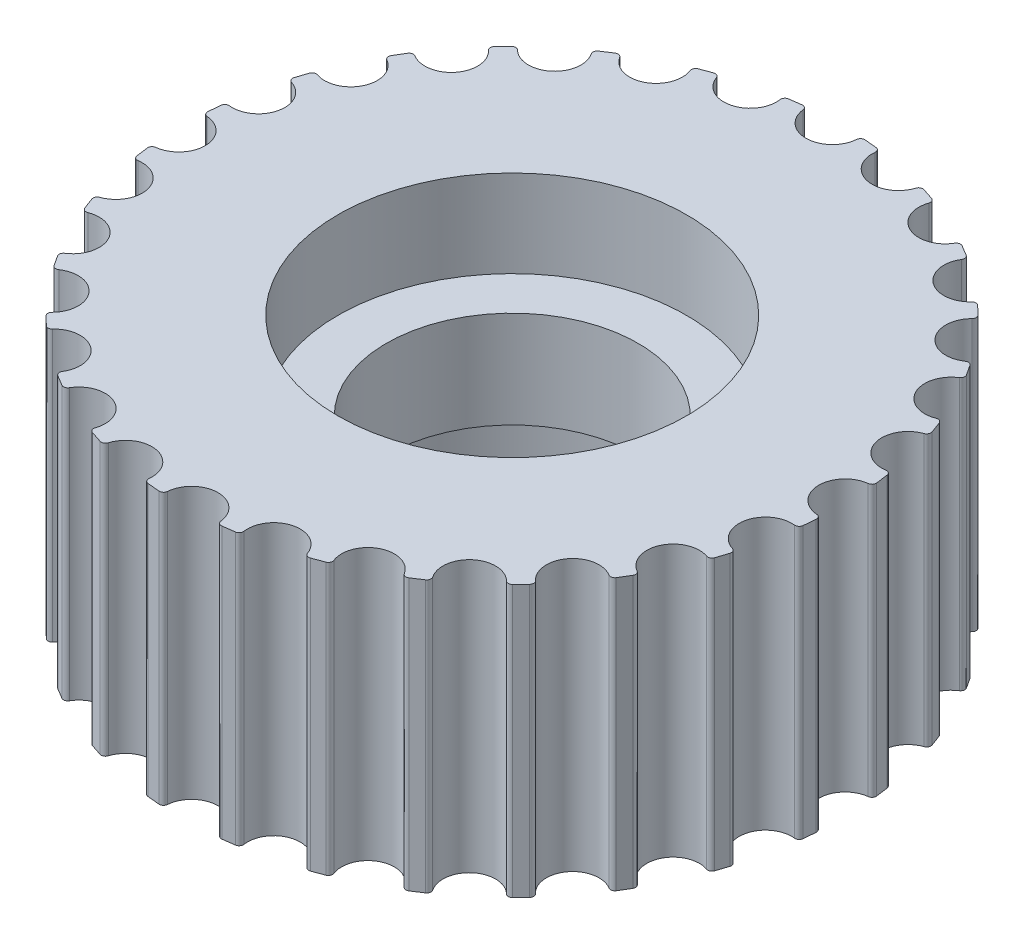
SolidWorks part; units mm, degrees
ref_plane "Front Plane" through (0, 0, 0) normal (0, 0, 1) x (1, 0, 0)
ref_plane "Top Plane" through (0, 0, 0) normal (0, 1, 0) x (1, 0, 0)
ref_plane "Right Plane" through (0, 0, 0) normal (1, 0, 0) x (0, 0, -1)
sketch "Sketch1" plane through (0, 0, 0) normal (0, 1, 0) x (1, 0, 0)
  line L0 (-1.2729, 8.4042) -> (-0.9622, 8.4454)
  line L1 (0.6306, 8.4766) -> (0.9426, 8.4476)
  line L2 (2.5024, 8.1236) -> (2.8002, 8.026)
  line L3 (4.2488, 7.363) -> (4.5174, 7.2015)
  line L4 (5.7821, 6.2329) -> (6.008, 6.0157)
  line L5 (7.0255, 4.7898) -> (7.1974, 4.5278)
  line L6 (7.9167, 3.1063) -> (8.026, 2.8126)
  line L7 (8.4108, 1.2667) -> (8.452, 0.9561)
  line L8 (8.4833, -0.6368) -> (8.4543, -0.9488)
  line L9 (8.1303, -2.5086) -> (8.0326, -2.8064)
  line L10 (7.3697, -4.255) -> (7.2082, -4.5235)
  line L11 (6.2395, -5.7883) -> (6.0223, -6.0142)
  line L12 (4.7965, -7.0317) -> (4.5345, -7.2036)
  line L13 (3.113, -7.9228) -> (2.8193, -8.0321)
  line L14 (1.2734, -8.417) -> (0.9627, -8.4582)
  line L15 (-0.6301, -8.4894) -> (-0.9421, -8.4605)
  line L16 (-2.5019, -8.1365) -> (-2.7997, -8.0388)
  line L17 (-4.2483, -7.3759) -> (-4.5169, -7.2144)
  line L18 (-5.7816, -6.2457) -> (-6.0075, -6.0285)
  line L19 (-7.025, -4.8027) -> (-7.1969, -4.5407)
  line L20 (-7.9162, -3.1192) -> (-8.0255, -2.8255)
  line L21 (-8.4103, -1.2796) -> (-8.4515, -0.9689)
  line L22 (-8.4828, 0.6239) -> (-8.4538, 0.9359)
  line L23 (-8.1298, 2.4957) -> (-8.0322, 2.7935)
  line L24 (-7.3692, 4.2421) -> (-7.2077, 4.5107)
  line L25 (-6.239, 5.7754) -> (-6.0219, 6.0013)
  line L26 (-4.796, 7.0189) -> (-4.534, 7.1908)
  line L27 (-3.1125, 7.91) -> (-2.8188, 8.0193)
  circle A0 centre (0, 0) radius 6.25
  circle A1 centre (0, 0) radius 7.75 construction
  circle A2 centre (0, 0) radius 8.5 construction
  circle A3 centre (0, 0) radius 8.78 construction
  arc A4 (-0.9622, 8.4454) -> (-0.8405, 8.3489) centre (-0.9498, 8.3361) cw
  arc A5 (-0.8405, 8.3489) -> (0.5127, 8.3754) centre (-0.1652, 8.4284) ccw
  arc A6 (0.5127, 8.3754) -> (0.6306, 8.4766) centre (0.6224, 8.3669) cw
  arc A7 (0.9426, 8.4476) -> (1.0398, 8.3265) centre (0.9304, 8.3383) cw
  arc A8 (1.0398, 8.3265) -> (2.365, 8.0513) centre (1.7159, 8.2537) ccw
  arc A9 (2.365, 8.0513) -> (2.5024, 8.1236) centre (2.47, 8.0185) cw
  arc A10 (2.8002, 8.026) -> (2.868, 7.8863) centre (2.764, 7.9221) cw
  arc A11 (2.868, 7.8863) -> (4.0987, 7.323) centre (3.5109, 7.6649) ccw
  arc A12 (4.0987, 7.323) -> (4.2488, 7.363) centre (4.1938, 7.2677) cw
  arc A13 (4.5174, 7.2015) -> (4.5524, 7.0503) centre (4.4589, 7.1083) cw
  arc A14 (4.5524, 7.0503) -> (5.6269, 6.2272) centre (5.1299, 6.6913) ccw
  arc A15 (5.6269, 6.2272) -> (5.7821, 6.2329) centre (5.7073, 6.1522) cw
  arc A16 (6.008, 6.0157) -> (6.0085, 5.8604) centre (5.9303, 5.9378) cw
  arc A17 (6.0085, 5.8604) -> (6.873, 4.8189) centre (6.4917, 5.3819) ccw
  arc A18 (6.873, 4.8189) -> (7.0255, 4.7898) centre (6.9347, 4.7278) cw
  arc A19 (7.1974, 4.5278) -> (7.1634, 4.3763) centre (7.1044, 4.4692) cw
  arc A20 (7.1634, 4.3763) -> (7.7744, 3.1686) centre (7.528, 3.8024) ccw
  arc A21 (7.7744, 3.1686) -> (7.9167, 3.1063) centre (7.8143, 3.0661) cw
  arc A22 (8.026, 2.8126) -> (7.959, 2.6725) centre (7.9222, 2.7762) cw
  arc A23 (7.959, 2.6725) -> (8.286, 1.3591) centre (8.1868, 2.0318) ccw
  arc A24 (8.286, 1.3591) -> (8.4108, 1.2667) centre (8.3021, 1.2502) cw
  arc A25 (8.452, 0.9561) -> (8.3556, 0.8344) centre (8.3427, 0.9436) cw
  arc A26 (8.3556, 0.8344) -> (8.3821, -0.5189) centre (8.4351, 0.159) ccw
  arc A27 (8.3821, -0.5189) -> (8.4833, -0.6368) centre (8.3736, -0.6286) cw
  arc A28 (8.4543, -0.9488) -> (8.3332, -1.046) centre (8.345, -0.9366) cw
  arc A29 (8.3332, -1.046) -> (8.0579, -2.3712) centre (8.2604, -1.7221) ccw
  arc A30 (8.0579, -2.3712) -> (8.1303, -2.5086) centre (8.0252, -2.4762) cw
  arc A31 (8.0326, -2.8064) -> (7.893, -2.8742) centre (7.9288, -2.7702) cw
  arc A32 (7.893, -2.8742) -> (7.3297, -4.1049) centre (7.6715, -3.5171) ccw
  arc A33 (7.3297, -4.1049) -> (7.3697, -4.255) centre (7.2744, -4.2) cw
  arc A34 (7.2082, -4.5235) -> (7.0569, -4.5586) centre (7.115, -4.4651) cw
  arc A35 (7.0569, -4.5586) -> (6.2339, -5.6331) centre (6.698, -5.1361) ccw
  arc A36 (6.2339, -5.6331) -> (6.2395, -5.7883) centre (6.1589, -5.7135) cw
  arc A37 (6.0223, -6.0142) -> (5.8671, -6.0147) centre (5.9445, -5.9365) cw
  arc A38 (5.8671, -6.0147) -> (4.8256, -6.8792) centre (5.3886, -6.4979) ccw
  arc A39 (4.8256, -6.8792) -> (4.7965, -7.0317) centre (4.7345, -6.9409) cw
  arc A40 (4.5345, -7.2036) -> (4.383, -7.1695) centre (4.4759, -7.1106) cw
  arc A41 (4.383, -7.1695) -> (3.1753, -7.7806) centre (3.809, -7.5341) ccw
  arc A42 (3.1753, -7.7806) -> (3.113, -7.9228) centre (3.0727, -7.8205) cw
  arc A43 (2.8193, -8.0321) -> (2.6792, -7.9652) centre (2.7828, -7.9284) cw
  arc A44 (2.6792, -7.9652) -> (1.3657, -8.2922) centre (2.0385, -8.1929) ccw
  arc A45 (1.3657, -8.2922) -> (1.2734, -8.417) centre (1.2569, -8.3082) cw
  arc A46 (0.9627, -8.4582) -> (0.841, -8.3618) centre (0.9503, -8.3489) cw
  arc A47 (0.841, -8.3618) -> (-0.5123, -8.3883) centre (0.1657, -8.4412) ccw
  arc A48 (-0.5123, -8.3883) -> (-0.6301, -8.4894) centre (-0.6219, -8.3797) cw
  arc A49 (-0.9421, -8.4605) -> (-1.0393, -8.3394) centre (-0.9299, -8.3512) cw
  arc A50 (-1.0393, -8.3394) -> (-2.3645, -8.0641) centre (-1.7154, -8.2666) ccw
  arc A51 (-2.3645, -8.0641) -> (-2.5019, -8.1365) centre (-2.4696, -8.0314) cw
  arc A52 (-2.7997, -8.0388) -> (-2.8675, -7.8991) centre (-2.7635, -7.935) cw
  arc A53 (-2.8675, -7.8991) -> (-4.0983, -7.3359) centre (-3.5104, -7.6777) ccw
  arc A54 (-4.0983, -7.3359) -> (-4.2483, -7.3759) centre (-4.1933, -7.2806) cw
  arc A55 (-4.5169, -7.2144) -> (-4.5519, -7.0631) centre (-4.4585, -7.1212) cw
  arc A56 (-4.5519, -7.0631) -> (-5.6265, -6.2401) centre (-5.1294, -6.7042) ccw
  arc A57 (-5.6265, -6.2401) -> (-5.7816, -6.2457) centre (-5.7069, -6.165) cw
  arc A58 (-6.0075, -6.0285) -> (-6.008, -5.8733) centre (-5.9298, -5.9507) cw
  arc A59 (-6.008, -5.8733) -> (-6.8725, -4.8318) centre (-6.4912, -5.3948) ccw
  arc A60 (-6.8725, -4.8318) -> (-7.025, -4.8027) centre (-6.9342, -4.7407) cw
  arc A61 (-7.1969, -4.5407) -> (-7.1629, -4.3892) centre (-7.1039, -4.482) cw
  arc A62 (-7.1629, -4.3892) -> (-7.7739, -3.1814) centre (-7.5275, -3.8152) ccw
  arc A63 (-7.7739, -3.1814) -> (-7.9162, -3.1192) centre (-7.8138, -3.0789) cw
  arc A64 (-8.0255, -2.8255) -> (-7.9585, -2.6854) centre (-7.9217, -2.789) cw
  arc A65 (-7.9585, -2.6854) -> (-8.2855, -1.3719) centre (-8.1863, -2.0446) ccw
  arc A66 (-8.2855, -1.3719) -> (-8.4103, -1.2796) centre (-8.3016, -1.2631) cw
  arc A67 (-8.4515, -0.9689) -> (-8.3551, -0.8472) centre (-8.3423, -0.9565) cw
  arc A68 (-8.3551, -0.8472) -> (-8.3816, 0.5061) centre (-8.4346, -0.1719) ccw
  arc A69 (-8.3816, 0.5061) -> (-8.4828, 0.6239) centre (-8.3731, 0.6157) cw
  arc A70 (-8.4538, 0.9359) -> (-8.3327, 1.0331) centre (-8.3445, 0.9237) cw
  arc A71 (-8.3327, 1.0331) -> (-8.0574, 2.3584) centre (-8.2599, 1.7092) ccw
  arc A72 (-8.0574, 2.3584) -> (-8.1298, 2.4957) centre (-8.0247, 2.4634) cw
  arc A73 (-8.0322, 2.7935) -> (-7.8925, 2.8613) centre (-7.9283, 2.7573) cw
  arc A74 (-7.8925, 2.8613) -> (-7.3292, 4.0921) centre (-7.671, 3.5042) ccw
  arc A75 (-7.3292, 4.0921) -> (-7.3692, 4.2421) centre (-7.2739, 4.1872) cw
  arc A76 (-7.2077, 4.5107) -> (-7.0565, 4.5457) centre (-7.1145, 4.4523) cw
  arc A77 (-7.0565, 4.5457) -> (-6.2334, 5.6203) centre (-6.6975, 5.1232) ccw
  arc A78 (-6.2334, 5.6203) -> (-6.239, 5.7754) centre (-6.1584, 5.7007) cw
  arc A79 (-6.0219, 6.0013) -> (-5.8666, 6.0018) centre (-5.944, 5.9237) cw
  arc A80 (-5.8666, 6.0018) -> (-4.8251, 6.8663) centre (-5.3881, 6.485) ccw
  arc A81 (-4.8251, 6.8663) -> (-4.796, 7.0189) centre (-4.734, 6.928) cw
  arc A82 (-4.534, 7.1908) -> (-4.3825, 7.1567) centre (-4.4754, 7.0977) cw
  arc A83 (-4.3825, 7.1567) -> (-3.1748, 7.7677) centre (-3.8085, 7.5213) ccw
  arc A84 (-3.1748, 7.7677) -> (-3.1125, 7.91) centre (-3.0723, 7.8076) cw
  arc A85 (-2.8188, 8.0193) -> (-2.6787, 7.9523) centre (-2.7823, 7.9155) cw
  arc A86 (-2.6787, 7.9523) -> (-1.3653, 8.2793) centre (-2.038, 8.1801) ccw
  arc A87 (-1.3653, 8.2793) -> (-1.2729, 8.4042) centre (-1.2564, 8.2954) cw
  point P233 (0.0002, -0.0064)
  dimension "D1" = 12.5
  dimension "D2" = 15.5
  dimension "D3" = 17
  dimension "D4" = 17.56
  dimension "D5" = 0.11
  dimension "D6" = 0.68
  dimension "D7" = 0.11
  dimension "D8" = 28
extrude "Boss-Extrude1" add sketch "Sketch1" along normal mid plane 7
sketch "Sketch2" plane through (0, 0, 0) normal (0, 1, 0) x (1, 0, 0)
  circle A0 centre (0, 0) radius 3.25
  circle A1 centre (0, 0) radius 4.5
  circle A2 centre (0, 0) radius 5.5
  circle A3 centre (0, 0) radius 6.25
  dimension "D1" = 11
  dimension "D2" = 9
  dimension "D3" = 6.5
extrude "Boss-Extrude2" add sketch "Sketch2" along normal mid plane 2.5 contours A3 A2 | A2 A1 | A1 A0 region at (-4.3727, 0, 0) region at (-5.3444, 0, 0) region at (-6.0732, 0, 0)
extrude "Boss-Extrude3" add sketch "Sketch2<3>" along normal mid plane 7 contours A2 A1 | A3 A2 region at (-5.3444, 0, 0) region at (-6.0732, 0, 0)
sketch "Sketch2<3>" plane through (0, 0, 0) normal (0, 1, 0) x (1, 0, 0) same geometry as "Sketch2"
